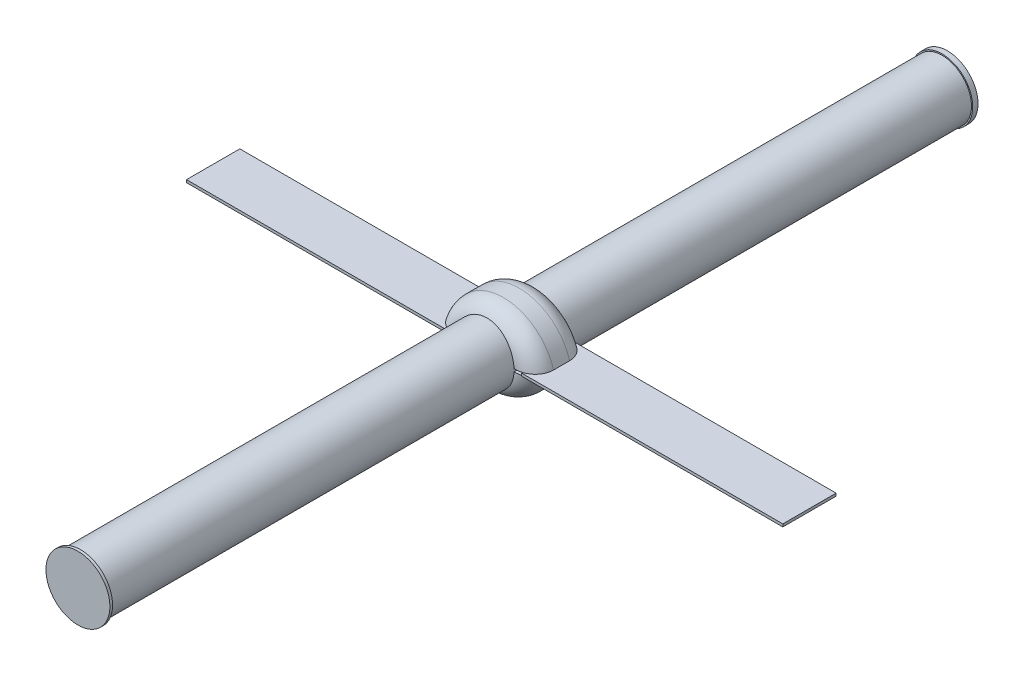
SolidWorks part; units mm, degrees
ref_plane "Front Plane" through (0, 0, 0) normal (0, 0, 1) x (1, 0, 0)
ref_plane "Top Plane" through (0, 0, 0) normal (0, 1, 0) x (1, 0, 0)
ref_plane "Right Plane" through (0, 0, 0) normal (1, 0, 0) x (0, 0, -1)
ref_plane "Plane1" through (0, 0, 10) normal (0, 0, 1) x (1, 0, 0)
sketch "Sketch1" plane through (0, 0, 10) normal (0, 0, 1) x (1, 0, 0)
  circle A0 centre (0, 0) radius 55.2
  dimension "D1" = 110.4
extrude "Boss-Extrude1" add sketch "Sketch1" along normal blind 798
sketch "Sketch3" plane through (0, 0, 808) normal (0, 0, 1) x (1, 0, 0)
  circle A0 centre (0, 0) radius 60
  dimension "D1" = 120
extrude "Boss-Extrude2" add sketch "Sketch3" along normal blind 5 contours A0
sketch "Sketch4" plane through (0, 0, 10) normal (0, 0, -1) x (-1, 0, 0)
  circle A0 centre (0, 0) radius 55.2
  dimension "D1" = 110.4
extrude "Boss-Extrude3" add sketch "Sketch4" along normal blind 20
sketch "Sketch5" plane through (0, 0, -10) normal (0, 0, -1) x (-1, 0, 0)
  circle A0 centre (0, 0) radius 55.2
  dimension "D1" = 110.4
extrude "Boss-Extrude4" add sketch "Sketch5" along normal blind 798
sketch "Sketch6" plane through (0, 0, -808) normal (0, 0, -1) x (-1, 0, 0)
  circle A0 centre (0, 0) radius 57.5
  dimension "D1" = 115
extrude "Boss-Extrude5" add sketch "Sketch6" along normal blind 10
sketch "Sketch10" plane through (0, 0, 0) normal (0, 0, 1) x (1, 0, 0)
  line L0 (-94.2708, 2.5) -> (-55.1434, 2.5)
  line L1 (55.1434, 2.5) -> (94.2708, 2.5)
  arc A0 (94.2708, 2.5) -> (-94.2708, 2.5) centre (0, -25) ccw
  arc A1 (55.1434, 2.5) -> (-55.1434, 2.5) centre (0, 0) ccw
  point P2 (0, 55.2)
  point P3 (0, -25)
  point P8 (0, 73.2)
  dimension "D1" = 55.2
  dimension "D2" = 18
  dimension "D3" = 0
  dimension "D4" = 25
  dimension "D5" = 2.5
extrude "Boss-Extrude8" add sketch "Sketch10" along normal mid plane 100
fillet "Fillet1" radius 35 1 edges at (0, 73.2, 50) type face fillet first side face at (0, 33.35, 50) second side face at (0, 37.85, 0)
fillet "Fillet2" radius 35 1 edges at (0, 73.2, -50) type face fillet first side face at (0, 33.35, -50) second side face at (0, 37.85, -17.5)
mirror "Mirror2" about plane through (0, 0, 0) normal (0, 1, 0) of "Fillet1", "Fillet2", "Boss-Extrude8"
ref_plane "Plane2" through (-94.2708, 0, 0) normal (-1, 0, 0) x (0, 0, 1)
ref_plane "Plane3" through (-69.2708, 0, 0) normal (-1, 0, 0) x (0, 0, 1)
sketch "Sketch11" plane through (-69.2708, 0, 0) normal (-1, 0, 0) x (0, 0, 1)
  line L1 (-50, 2.5) -> (50, 2.5)
  line L2 (-50, 2.5) -> (-50, -2.5)
  line L3 (-50, -2.5) -> (50, -2.5)
  line L4 (50, 2.5) -> (50, -2.5)
extrude "Boss-Extrude9" add sketch "Sketch11" along normal blind 490
mirror "Mirror3" about plane through (0, 0, 0) normal (1, 0, 0) of "Boss-Extrude9"
